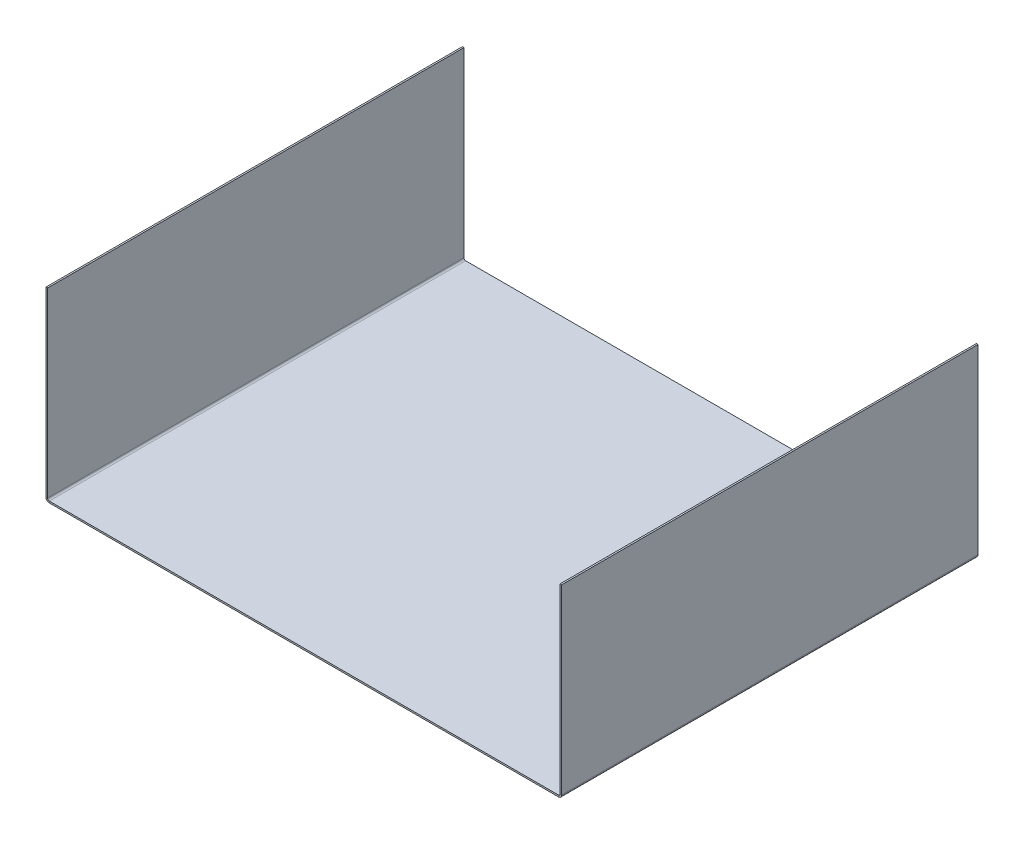
SolidWorks part; units mm, degrees
note: The reader was unsure of these and kept them because the rebuilt part matched: flange length of "Edge-Flange1".
ref_plane "Front Plane" through (0, 0, 0) normal (0, 0, 1) x (1, 0, 0)
ref_plane "Top Plane" through (0, 0, 0) normal (0, 1, 0) x (1, 0, 0)
ref_plane "Right Plane" through (0, 0, 0) normal (1, 0, 0) x (0, 0, -1)
sketch "Sketch1" plane through (0, 0, 0) normal (0, 1, 0) x (1, 0, 0)
  line L1 (111.5, 90) -> (-111.5, 90)
  line L2 (111.5, 90) -> (111.5, -90)
  line L3 (111.5, -90) -> (-111.5, -90)
  line L4 (-111.5, 90) -> (-111.5, -90)
  line L5 (111.5, 90) -> (-111.5, -90) construction
  line L6 (111.5, -90) -> (-111.5, 90) construction
  point P0 (0, 0)
  dimension "D1" = 223
  dimension "D2" = 180
base flange "Base-Flange1" sketch "Sketch1" thickness 0.7 reverse thickness direction no parameters "D1"=0.7366
edge flange "Edge-Flange1" sketch "Sketch10" flange profiles "Sketch10", "Sketch11" flange angle 90 flange length 80.1366 flange position material inside bend radius 0.7366 thickness 0.7 relief rectangular parameters "D6"=10, "D8"=1
sketch "Sketch10" plane through (-111.5, 0, 0) normal (-1, 0, 0) x (0, 0, 1)
  line L0 (-90, 0) -> (90, 0) construction
  line L1 (-90, 0) -> (90, 0)
  line L2 (-90, 0) -> (-90, 79.4366)
  line L3 (-90, 79.4366) -> (90, 79.4366)
  line L4 (90, 79.4366) -> (90, 0)
sketch "Sketch11" plane through (111.5, 0, 0) normal (1, 0, 0) x (0, 0, -1)
  line L0 (-90, 0) -> (90, 0) construction
  line L1 (-90, 0) -> (90, 0)
  line L2 (-90, 0) -> (-90, 79.4366)
  line L3 (-90, 79.4366) -> (90, 79.4366)
  line L4 (90, 79.4366) -> (90, 0)
bend "EdgeBend1" bend radius 0.7366 bend angle 90 parameters "D5"=1
bend "EdgeBend2" bend radius 0.7366 bend angle 90 parameters "D5"=2
sketch "Bend-Lines1" [suppressed] plane through (0, 0, 0) normal (0, 1, 0) x (1, 0, 0)
sketch "Bounding-Box1" [suppressed] plane through (0, 0, 0) normal (0, 1, 0) x (1, 0, 0)
sheet metal parameters "Sheet-Metal1" thickness 0.7 parameters "D1"=0.7366
flat pattern "Flat-Pattern1" [suppressed]
sketch "Bend-Lines2" plane through (0, 0, 0) normal (0, 1, 0) x (1, 0, 0)
sketch3d "Bounding-Box2" [suppressed]
  line L0 (-111.5, 90, 0) -> (111.5, 90, 0) construction
  line L1 (-111.5, -90, 0) -> (111.5, -90, 0) construction
  line L2 (-111.5, 90, 0) -> (-111.5, -90, 0) construction
  line L3 (111.5, 90, 0) -> (111.5, -90, 0) construction
sheet metal parameters "Sheet-Metal2" thickness 0.7 parameters "D1"=0.7366
flat pattern "Flat-Pattern1"
sketch "Bend-Lines2" plane through (0, 0, 0) normal (0, 1, 0) x (1, 0, 0)
  line L0 (110.9168, -90) -> (110.9168, 90) construction
  line L1 (-110.9168, 90) -> (-110.9168, -90) construction
  line L2 (110.9168, -90) -> (110.9168, 90) construction
  line L3 (-110.9168, 90) -> (-110.9168, -90) construction
sketch3d "Bounding-Box2" [suppressed]
  line L0 (190.4702, 90, 0) -> (-190.4702, 90, 0) construction
  line L1 (190.4702, -90, 0) -> (-190.4702, -90, 0) construction
  line L2 (190.4702, 90, 0) -> (190.4702, -90, 0) construction
  line L3 (-190.4702, 90, 0) -> (-190.4702, -90, 0) construction
bend of the flat pattern "Flatten-<EdgeBend1>1"
bend of the flat pattern "Flatten-<EdgeBend2>1"
